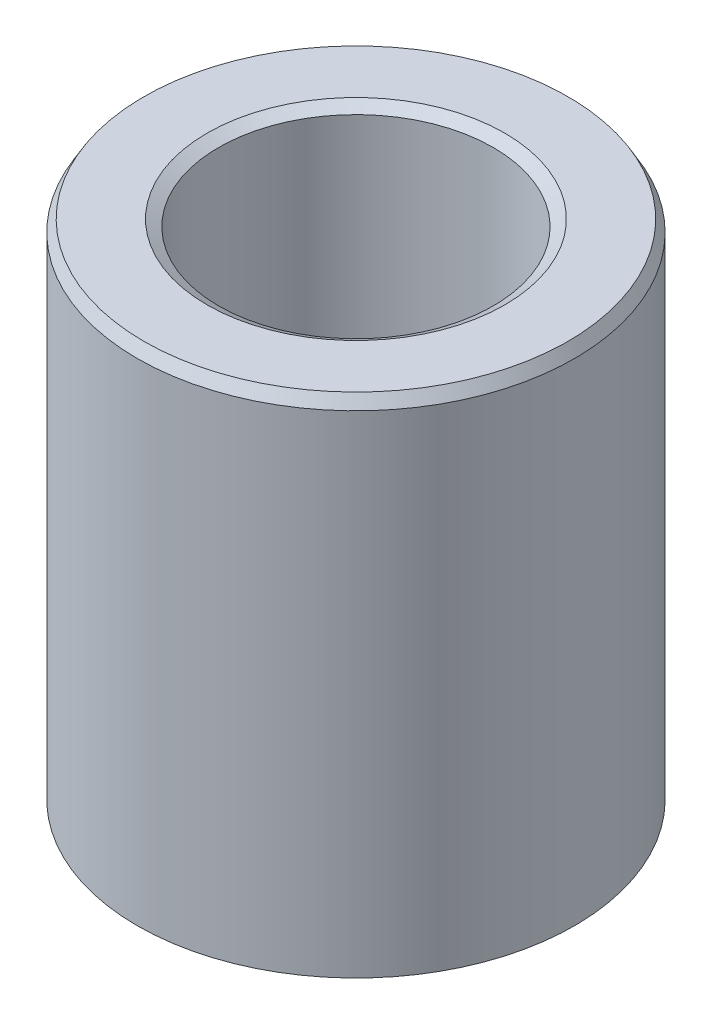
SolidWorks part; units mm, degrees
ref_plane "Front Plane" through (0, 0, 0) normal (0, 0, 1) x (1, 0, 0)
ref_plane "Top Plane" through (0, 0, 0) normal (0, 1, 0) x (1, 0, 0)
ref_plane "Right Plane" through (0, 0, 0) normal (1, 0, 0) x (0, 0, -1)
sketch "Sketch1" plane through (0, 0, 0) normal (0, 1, 0) x (1, 0, 0)
  circle A0 centre (0, 0) radius 57.5
  dimension "SLEEVE_OD" = 115
extrude "Boss-Extrude1" add sketch "Sketch1" along normal blind 133.9774
sketch "Sketch2" plane through (0, 0, 0) normal (0, 1, 0) x (1, 0, 0)
  circle A0 centre (0, 0) radius 36.1081
  dimension "BORE_D" = 72.2161
extrude "Cut-Extrude1" cut sketch "Sketch2" along normal through all
chamfer "Chamfer1" distance 3.0316 angle 30 4 edges at (0, 133.9774, 36.1081) (0, 0, 36.1081) (0, 0, 57.5) (0, 133.9774, 57.5) first distance on face at (0, 133.9774, 36.1081) first distance on face at (0, 0, 36.1081) first distance on face at (0, 133.9774, 57.5)
